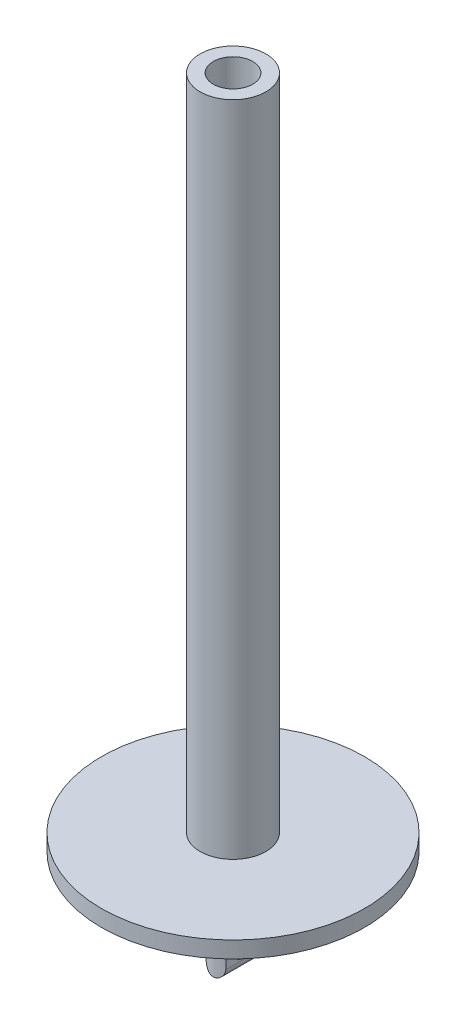
SolidWorks part; units mm, degrees
material "201.0-T43, per stampo in conchiglia (SS)"
ref_plane "Piano frontale" through (0, 0, 0) normal (0, 0, 1) x (1, 0, 0)
ref_plane "Piano superiore" through (0, 0, 0) normal (0, 1, 0) x (1, 0, 0)
ref_plane "Piano destro" through (0, 0, 0) normal (1, 0, 0) x (0, 0, -1)
sketch "Schizzo1" plane through (0, 0, 0) normal (0, 1, 0) x (1, 0, 0)
  circle A0 centre (0, 0) radius 6
extrude "Estrusione-Estrusione1" add sketch "Schizzo1" along normal blind 30
sketch "Schizzo2" plane through (0, 30, 0) normal (0, 1, 0) x (1, 0, 0)
  circle A0 centre (0, 0) radius 40
extrude "Estrusione-Estrusione2" add sketch "Schizzo2" along normal blind 5
sketch "Schizzo3" plane through (0, 35, 0) normal (0, 1, 0) x (1, 0, 0)
  circle A0 centre (0, 0) radius 10
extrude "Estrusione-Estrusione3" add sketch "Schizzo3" along normal blind 200
sketch "Schizzo4" plane through (0, 235, 0) normal (0, 1, 0) x (1, 0, 0)
  circle A0 centre (0, 0) radius 6
extrude "Taglio-Estrusione1" cut sketch "Schizzo4" against normal blind 160
sketch "Schizzo5" plane through (0, 0, 0) normal (0, 0, 1) x (1, 0, 0)
  line L1 (6, 0) -> (3, 0)
  line L2 (6, 0) -> (6, 13)
  line L3 (6, 13) -> (3, 13)
  line L4 (3, 0) -> (3, 13)
  dimension "D1" = 13
  dimension "D2" = 3
extrude "Taglio-Estrusione2" cut sketch "Schizzo5" against normal through all and the other way through all
mirror "Specchia1" about plane through (0, 0, 0) normal (1, 0, 0) of "Taglio-Estrusione2"
ref_plane "Piano1" through (0, 0, 0) normal (1, 0, 0) x (0, 0, -1)
sketch "Schizzo6" plane through (0, 0, 0) normal (1, 0, 0) x (0, 0, -1)
  line L0 (-4, 6.0588) -> (4, 6.0588)
  arc A0 (4, 6.0588) -> (-4, 6.0588) centre (0, 6.0588) ccw
  dimension "D1" = 4
  dimension "D2" = 8
revolve "Rivoluzione1" add sketch "Schizzo6" angle 360 about L0
combine bodies "Abbina1" operation type subtract main body 106 bodies to subtract 107
fillet "Raccordo1" radius 3 4 edges at (3, 0, 0) (-3, 0, 0) (-3, 13, 0) (3, 13, 0)
